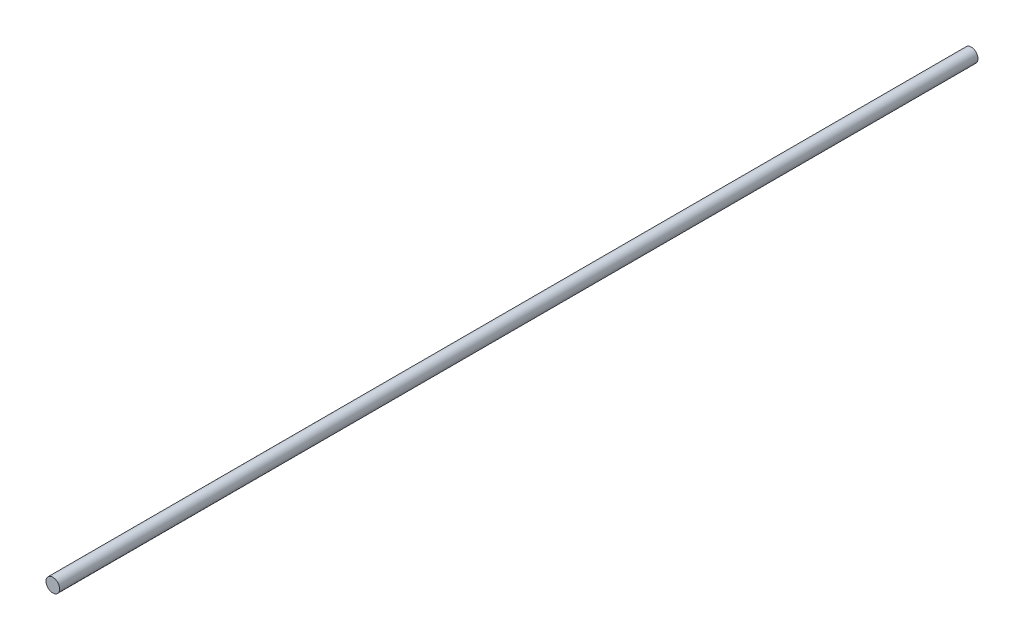
SolidWorks part; units mm, degrees
material "AISI 347 Annealed Stainless Steel (SS)"
ref_plane "Front Plane" through (0, 0, 0) normal (0, 0, 1) x (1, 0, 0)
ref_plane "Top Plane" through (0, 0, 0) normal (0, 1, 0) x (1, 0, 0)
ref_plane "Right Plane" through (0, 0, 0) normal (1, 0, 0) x (0, 0, -1)
sketch "Sketch1" plane through (0, 0, 0) normal (0, 0, 1) x (1, 0, 0)
  circle A0 centre (0, 0) radius 5
  dimension "D1" = 10
extrude "Boss-Extrude1" add sketch "Sketch1" along normal blind 674
